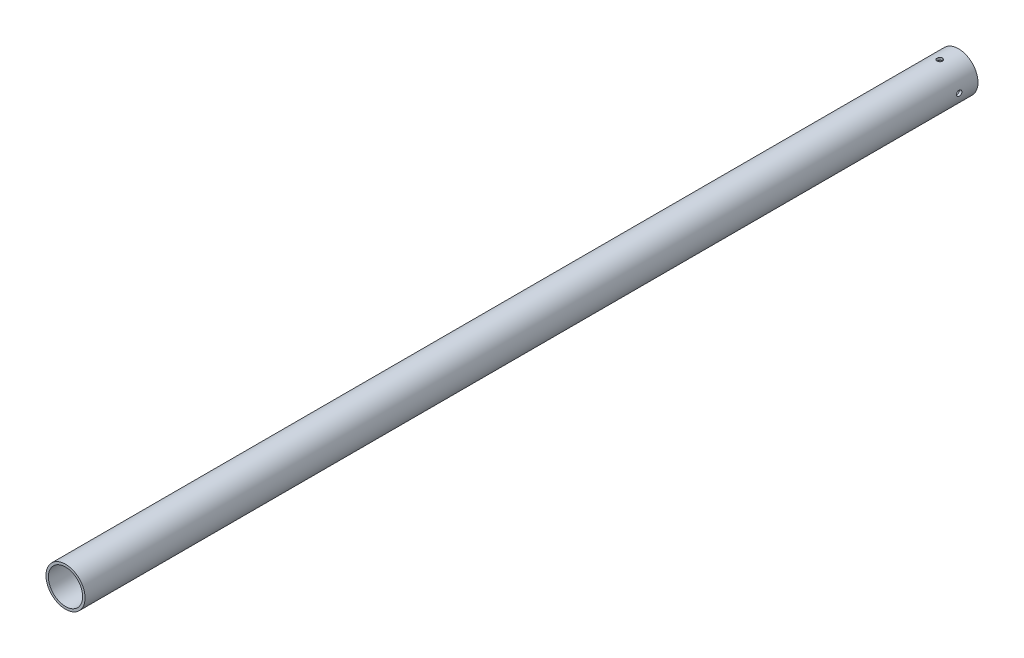
SolidWorks part; units mm, degrees
material "PC High Viscosity"
ref_plane "Front Plane" through (0, 0, 0) normal (0, 0, 1) x (1, 0, 0)
ref_plane "Top Plane" through (0, 0, 0) normal (0, 1, 0) x (1, 0, 0)
ref_plane "Right Plane" through (0, 0, 0) normal (1, 0, 0) x (0, 0, -1)
sketch "Sketch2" plane through (0, 0, 0) normal (0, 0, 1) x (1, 0, 0)
  circle A0 centre (0, 0) radius 11.1125
  circle A1 centre (0, 0) radius 12.7
  dimension "D1" = 25.4
  dimension "D2" = 22.225
extrude "Boss-Extrude1" add sketch "Sketch2" along normal mid plane 579.8248
sketch "Sketch3" plane through (0, 0, 0) normal (0, 1, 0) x (1, 0, 0)
  line L0 (12.7, 289.9124) -> (-12.7, 289.9124) construction
  circle A0 centre (0, 277.7204) radius 1.7526
  point P5 (0, 0)
  dimension "D1" = 3.5052
  dimension "D2" = 12.192
extrude "Cut-Extrude1" cut sketch "Sketch3" against normal through all both and the other way through all
sketch "Sketch5" plane through (0, 0, 0) normal (1, 0, 0) x (0, 0, -1)
  line L0 (289.9124, -12.7) -> (289.9124, 12.7) construction
  circle A0 centre (277.7204, 0) radius 1.7526
  point P5 (0, 0)
  dimension "D1" = 3.5052
  dimension "D2" = 12.192
extrude "Cut-Extrude2" cut sketch "Sketch5" against normal through all both and the other way through all
